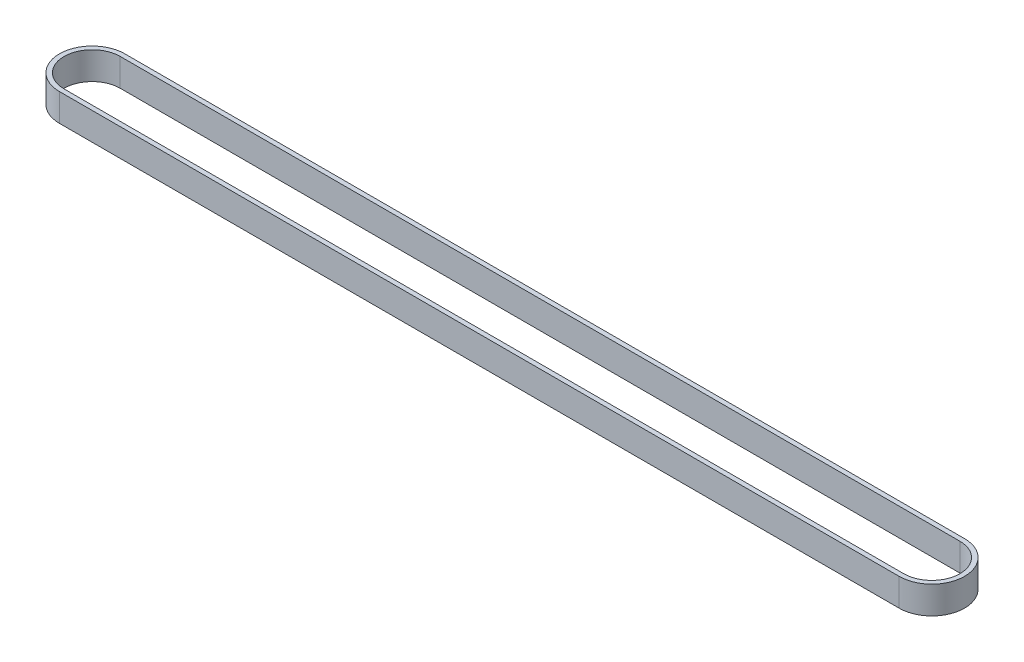
SolidWorks part; units mm, degrees
ref_plane "Front Plane" through (0, 0, 0) normal (0, 0, 1) x (1, 0, 0)
ref_plane "Top Plane" through (0, 0, 0) normal (0, 1, 0) x (1, 0, 0)
ref_plane "Right Plane" through (0, 0, 0) normal (1, 0, 0) x (0, 0, -1)
sketch "Sketch1" plane through (0, 0, 0) normal (0, 1, 0) x (1, 0, 0)
  line L0 (0, 0) -> (182.64, 0) construction
  line L1 (0, 6.1122) -> (182.64, 6.1122)
  line L2 (0, -6.1122) -> (182.64, -6.1122)
  line L3 (91.32, 0) -> (91.32, 14.2675) construction
  line L4 (0, 7.11) -> (182.64, 7.11)
  line L5 (0, -7.11) -> (182.64, -7.11)
  arc A0 (0, 6.1122) -> (0, -6.1122) centre (0, 0) ccw
  arc A1 (182.64, -6.1122) -> (182.64, 6.1122) centre (182.64, 0) ccw
  arc A2 (0, 7.11) -> (0, -7.11) centre (0, 0) ccw
  arc A3 (182.64, 7.11) -> (182.64, -7.11) centre (182.64, 0) cw
  dimension "D1" = 12.2244
  dimension "D3" = 7.11
  dimension "D2" = 182.64
extrude "Boss-Extrude1" add sketch "Sketch1" along normal blind 6
